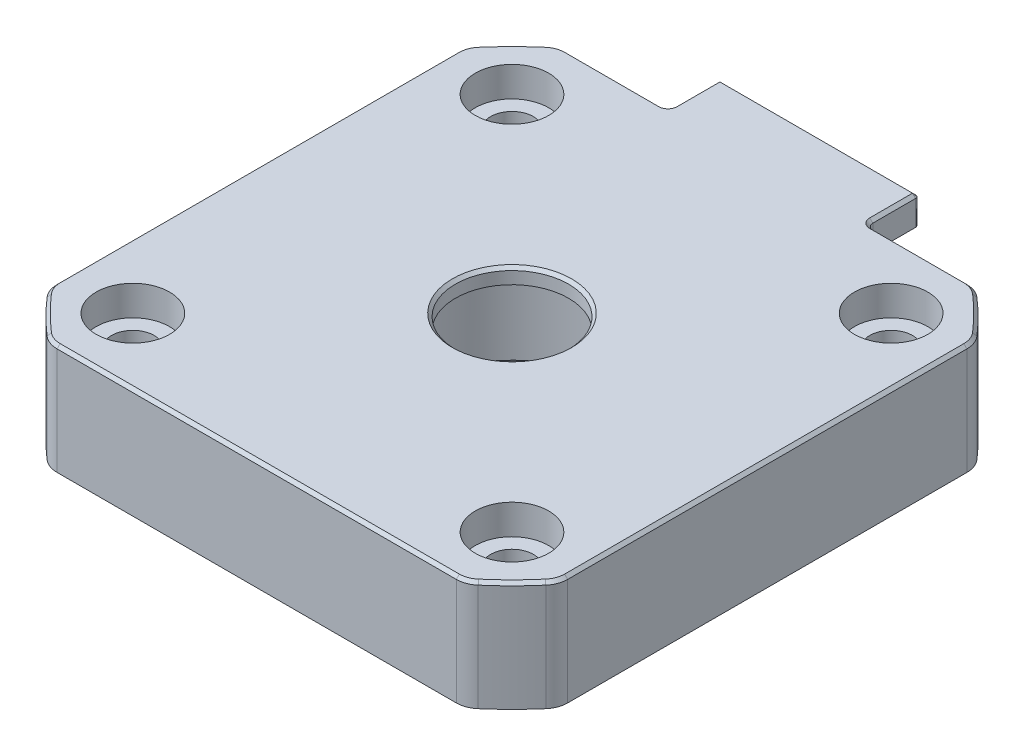
SolidWorks part; units mm, degrees
ref_plane "Front" through (0, 0, 0) normal (0, 0, 1) x (1, 0, 0)
ref_plane "Top" through (0, 0, 0) normal (0, 1, 0) x (1, 0, 0)
ref_plane "Right" through (0, 0, 0) normal (1, 0, 0) x (0, 0, -1)
ref_plane "Plane1" through (0, 6.7, 0) normal (0, -1, 0) x (1, 0, 0)
sketch "Sketch1" plane through (0, 6.7, 0) normal (0, -1, 0) x (1, 0, 0)
  line L0 (8.625, -20.875) -> (16.3168, -20.875)
  line L1 (20.875, -16.3168) -> (20.875, 16.3168)
  line L2 (16.3168, 20.875) -> (-16.3168, 20.875)
  line L3 (-20.875, 16.3168) -> (-20.875, -16.3168)
  line L4 (-16.3168, -20.875) -> (-8.625, -20.875)
  line L5 (-8.125, -21.375) -> (-8.125, -24.875)
  line L6 (-7.875, -25.125) -> (7.875, -25.125)
  line L7 (8.125, -24.875) -> (8.125, -21.375)
  line L8 (0, -25.125) -> (0, 0) construction
  line L9 (0, 0) -> (-20.875, 0) construction
  arc A0 (16.3168, -20.875) -> (17.6247, -20.388) centre (16.3168, -18.875) ccw
  arc A1 (17.6247, -20.388) -> (20.388, -17.6247) centre (0, 0) ccw
  arc A2 (20.388, -17.6247) -> (20.875, -16.3168) centre (18.875, -16.3168) ccw
  arc A3 (20.875, 16.3168) -> (20.388, 17.6247) centre (18.875, 16.3168) ccw
  arc A4 (20.388, 17.6247) -> (17.6247, 20.388) centre (0, 0) ccw
  arc A5 (17.6247, 20.388) -> (16.3168, 20.875) centre (16.3168, 18.875) ccw
  arc A6 (-16.3168, 20.875) -> (-17.6247, 20.388) centre (-16.3168, 18.875) ccw
  arc A7 (-17.6247, 20.388) -> (-20.388, 17.6247) centre (0, 0) ccw
  arc A8 (-20.388, 17.6247) -> (-20.875, 16.3168) centre (-18.875, 16.3168) ccw
  arc A9 (-20.875, -16.3168) -> (-20.388, -17.6247) centre (-18.875, -16.3168) ccw
  arc A10 (-20.388, -17.6247) -> (-17.6247, -20.388) centre (0, 0) ccw
  arc A11 (-17.6247, -20.388) -> (-16.3168, -20.875) centre (-16.3168, -18.875) ccw
  arc A12 (-8.125, -24.875) -> (-7.875, -25.125) centre (-7.875, -24.875) ccw
  arc A13 (7.875, -25.125) -> (8.125, -24.875) centre (7.875, -24.875) ccw
  arc A14 (-8.625, -20.875) -> (-8.125, -21.375) centre (-8.625, -21.375) cw
  arc A15 (8.625, -20.875) -> (8.125, -21.375) centre (8.625, -21.375) ccw
  dimension "D3" = 26.95
  dimension "D4" = 2
  dimension "D7" = 0.25
  dimension "D8" = 0.5
  dimension "D1" = 41.75
  dimension "D2" = 41.75
  dimension "D5" = 16.25
  dimension "D6" = 4.25
extrude "Boss-Extrude1" add sketch "Sketch1" against normal blind 2.3
sketch "Sketch2" plane through (0, 6.7, 0) normal (0, -1, 0) x (1, 0, 0)
  line L0 (-8.2, -19.7914) -> (-8.2, -20.875)
  line L1 (-8.2, -20.875) -> (-16.3168, -20.875)
  line L2 (-20.875, -16.3168) -> (-20.875, 16.3168)
  line L3 (-16.3168, 20.875) -> (16.3168, 20.875)
  line L4 (20.875, 16.3168) -> (20.875, -16.3168)
  line L5 (16.3168, -20.875) -> (8.2, -20.875)
  line L6 (8.2, -20.875) -> (8.2, -19.7914)
  line L7 (8.4929, -19.0843) -> (19.2071, -8.3701)
  line L8 (19.5, -7.663) -> (19.5, 7.663)
  line L9 (19.2071, 8.3701) -> (8.3701, 19.2071)
  line L10 (7.663, 19.5) -> (-7.663, 19.5)
  line L11 (-8.3701, 19.2071) -> (-19.2071, 8.3701)
  line L12 (-19.5, 7.663) -> (-19.5, -7.663)
  line L13 (-19.2071, -8.3701) -> (-8.4929, -19.0843)
  arc A0 (-16.3168, -20.875) -> (-17.6247, -20.388) centre (-16.3168, -18.875) cw
  arc A1 (-17.6247, -20.388) -> (-20.388, -17.6247) centre (0, 0) cw
  arc A2 (-20.388, -17.6247) -> (-20.875, -16.3168) centre (-18.875, -16.3168) cw
  arc A3 (-20.875, 16.3168) -> (-20.388, 17.6247) centre (-18.875, 16.3168) cw
  arc A4 (-20.388, 17.6247) -> (-17.6247, 20.388) centre (0, 0) cw
  arc A5 (-17.6247, 20.388) -> (-16.3168, 20.875) centre (-16.3168, 18.875) cw
  arc A6 (16.3168, 20.875) -> (17.6247, 20.388) centre (16.3168, 18.875) cw
  arc A7 (17.6247, 20.388) -> (20.388, 17.6247) centre (0, 0) cw
  arc A8 (20.388, 17.6247) -> (20.875, 16.3168) centre (18.875, 16.3168) cw
  arc A9 (20.875, -16.3168) -> (20.388, -17.6247) centre (18.875, -16.3168) cw
  arc A10 (20.388, -17.6247) -> (17.6247, -20.388) centre (0, 0) cw
  arc A11 (17.6247, -20.388) -> (16.3168, -20.875) centre (16.3168, -18.875) cw
  arc A12 (8.2, -19.7914) -> (8.4929, -19.0843) centre (9.2, -19.7914) cw
  arc A13 (19.2071, -8.3701) -> (19.5, -7.663) centre (18.5, -7.663) ccw
  arc A14 (19.5, 7.663) -> (19.2071, 8.3701) centre (18.5, 7.663) ccw
  arc A15 (8.3701, 19.2071) -> (7.663, 19.5) centre (7.663, 18.5) ccw
  arc A16 (-7.663, 19.5) -> (-8.3701, 19.2071) centre (-7.663, 18.5) ccw
  arc A17 (-19.2071, 8.3701) -> (-19.5, 7.663) centre (-18.5, 7.663) ccw
  arc A18 (-19.5, -7.663) -> (-19.2071, -8.3701) centre (-18.5, -7.663) ccw
  arc A19 (-8.4929, -19.0843) -> (-8.2, -19.7914) centre (-9.2, -19.7914) cw
extrude "Boss-Extrude2" add sketch "Sketch2" along normal blind 6.7
sketch "Sketch3" plane through (0, 6.7, 0) normal (0, -1, 0) x (1, 0, 0)
  line L0 (-11.8097, -15.7675) -> (-15.7675, -11.8097)
  line L1 (-15.7675, 11.8097) -> (-11.8097, 15.7675)
  line L2 (15.7675, -11.8097) -> (11.8097, -15.7675)
  line L3 (11.8097, 15.7675) -> (15.7675, 11.8097)
  arc A0 (-15.7675, -11.8097) -> (-11.8097, -15.7675) centre (-15.5, -15.5) cw
  arc A1 (-11.8097, 15.7675) -> (-15.7675, 11.8097) centre (-15.5, 15.5) cw
  arc A2 (11.8097, -15.7675) -> (15.7675, -11.8097) centre (15.5, -15.5) cw
  arc A3 (15.7675, 11.8097) -> (11.8097, 15.7675) centre (15.5, 15.5) cw
extrude "Boss-Extrude3" add sketch "Sketch3" along normal blind 0.5
sketch "Sketch4" plane through (0, 6.7, 0) normal (0, -1, 0) x (1, 0, 0)
  circle A0 centre (0, 0) radius 12.925
extrude "Boss-Extrude4" add sketch "Sketch4" along normal blind 7.6
draft "Draft1" type of draft neutral plane draft angle 56.31 faces to draft 1 face at (-13.3361, 6.45, -13.3361) neutral plane through (-15.5, 6.2, -15.5) neutral plane normal (0, -1, 0) parameters "D1"=56.31
draft "Draft2" type of draft neutral plane draft angle 56.31 faces to draft 1 face at (-13.3361, 6.45, 13.3361) neutral plane through (-15.5, 6.2, 15.5) neutral plane normal (0, -1, 0) parameters "D1"=56.31
draft "Draft3" type of draft neutral plane draft angle 56.31 faces to draft 1 face at (13.3361, 6.45, 13.3361) neutral plane through (15.5, 6.2, 15.5) neutral plane normal (0, -1, 0) parameters "D1"=56.31
draft "Draft4" type of draft neutral plane draft angle 56.31 faces to draft 1 face at (13.3361, 6.45, -13.3361) neutral plane through (15.5, 6.2, -15.5) neutral plane normal (0, -1, 0) parameters "D1"=56.31
sketch "Sketch5" plane through (0, -0.9, 0) normal (0, -1, 0) x (1, 0, 0)
  circle A0 centre (0, 0) radius 8.025
extrude "Cut-Extrude1" cut sketch "Sketch5" against normal blind 8
sketch "Sketch6" plane through (0, 6.7, 0) normal (0, -1, 0) x (1, 0, 0)
  line L0 (6.95, -16.775) -> (-6.95, -16.775)
  line L1 (-7.2, -17.025) -> (-7.2, -23.925)
  line L2 (-6.95, -24.175) -> (6.95, -24.175)
  line L3 (7.2, -23.925) -> (7.2, -17.025)
  arc A0 (-6.95, -16.775) -> (-7.2, -17.025) centre (-6.95, -17.025) ccw
  arc A1 (-7.2, -23.925) -> (-6.95, -24.175) centre (-6.95, -23.925) ccw
  arc A2 (6.95, -24.175) -> (7.2, -23.925) centre (6.95, -23.925) ccw
  arc A3 (7.2, -17.025) -> (6.95, -16.775) centre (6.95, -17.025) ccw
extrude "Cut-Extrude2" cut sketch "Sketch6" against normal blind 1.65
hole_wizard "CBORE for M8 Hex Head Bolt1" positions "Sketch8" profile "Sketch7" counterbore size "M8" standard "ANSI Metric"
sketch "Sketch8" plane through (0, 7.1, 0) normal (0, -1, 0) x (-1, 0, 0)
  point P0 (0, 0)
sketch "Sketch7" plane through (0, 7.1, 0) normal (1, 0, 0) x (0, 0, -1)
  line L0 (0, 0) -> (0, 1.9)
  line L1 (0, 1.9) -> (4.625, 1.9)
  line L3 (4.625, 1.9) -> (4.625, 0.65)
  line L4 (4.625, 0.65) -> (6, 0.65)
  line L5 (6, 0.65) -> (6, 0)
  line L7 (6, 0) -> (0, 0)
  line L11 (0, -6.35) -> (0, 107.95) construction
  dimension "Thru Hole Dia." = 9.25
  dimension "Thru Hole Depth" = 1.9
  dimension "C'Bore Dia." = 12
  dimension "C'Bore Depth" = 0.65
hole_wizard "CBORE for M3 Hex Head Machine Screw1" positions "Sketch10" profile "Sketch9" counterbore size "M3" standard "ANSI Metric"
sketch "Sketch10" plane through (0, 9, 0) normal (0, 1, 0) x (1, 0, 0)
  point P0 (15.5, 15.5)
  point P1 (15.5, -15.5)
  point P2 (-15.5, 15.5)
  point P3 (-15.5, -15.5)
sketch "Sketch9" plane through (15.5, 9, -15.5) normal (1, 0, 0) x (0, 0, 1)
  line L0 (0, 0) -> (0, 9.9)
  line L1 (0, 9.9) -> (1.75, 9.9)
  line L3 (1.75, 9.9) -> (1.75, 2.45)
  line L4 (1.75, 2.45) -> (3, 2.45)
  line L5 (3, 2.45) -> (3, 0)
  line L7 (3, 0) -> (0, 0)
  line L11 (0, -6.35) -> (0, 107.95) construction
  dimension "Thru Hole Dia." = 3.5
  dimension "Thru Hole Depth" = 9.9
  dimension "C'Bore Dia." = 6
  dimension "C'Bore Depth" = 2.45
chamfer "Chamfer1" distance 0.25 angle 45 27 edges at (0, 9, -4.625) (12.4709, 9, -20.875) (17.0146, 9, -20.7493) (8.2714, 9, -21.0214) (19.0565, 9, -19.0565) (8.125, 9, -23.125) (20.7493, 9, -17.0146) (8.0518, 9, -25.0518) (20.875, 9, 0) (0, 9, -25.125) (20.7493, 9, 17.0146) (-8.0518, 9, -25.0518) (19.0565, 9, 19.0565) (-8.125, 9, -23.125) (17.0146, 9, 20.7493) (-8.2714, 9, -21.0214) (0, 9, 20.875) (-12.4709, 9, -20.875) (-17.0146, 9, 20.7493) (-17.0146, 9, -20.7493) (-19.0565, 9, 19.0565) (-19.0565, 9, -19.0565) (-20.7493, 9, 17.0146) (-20.7493, 9, -17.0146) (-20.875, 9, 0) (0, 7.1, -6) (0, -0.9, -12.925)
chamfer "Chamfer4" distance 0.5 angle 60.945 1 edges at (0, -0.9, 8.025) first distance on face at (0, -0.9, -12.675)
fillet "Fillet1" radius 0.15 1 edges at (0, 6.7, -12.925) tangent propagation no
fillet "Fillet2" radius 0.5 3 edges at (-12.3534, 6.7, -12.3534) (12.3534, 6.7, -12.3534) (12.8837, 6.2, -12.8837) tangent propagation no
